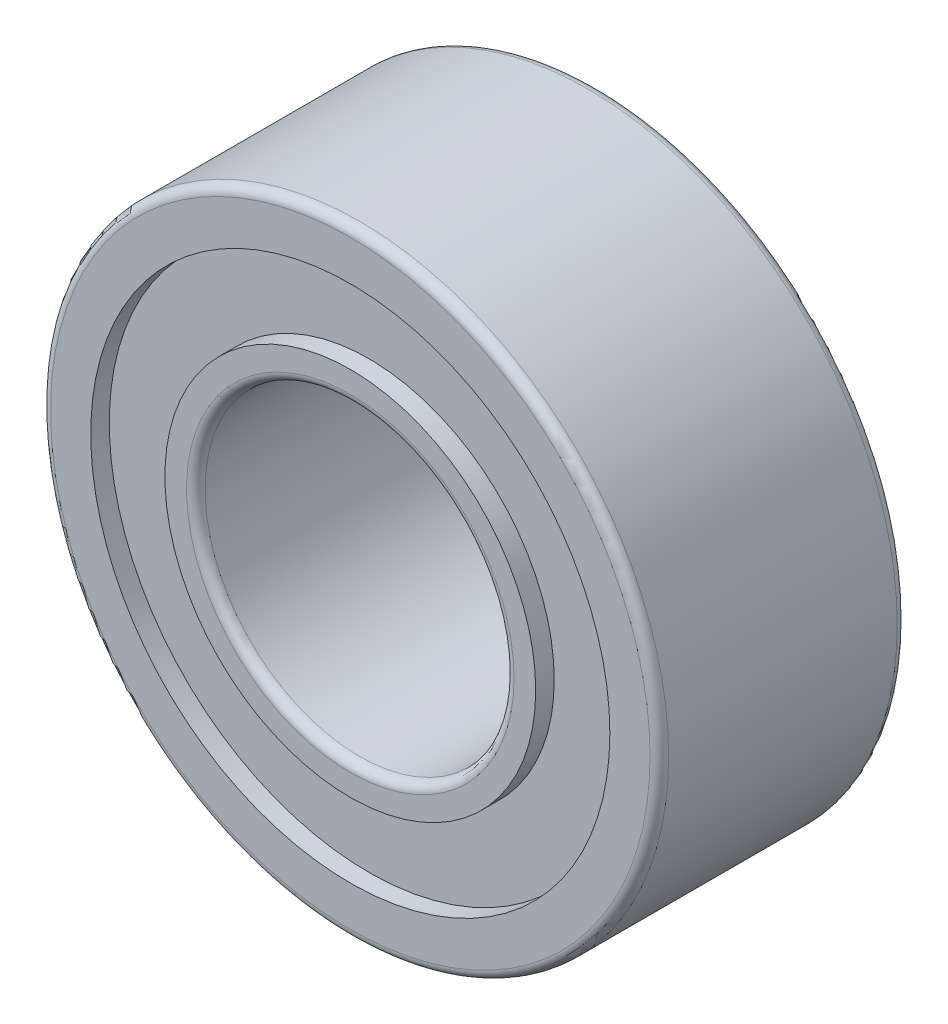
SolidWorks part; units mm, degrees
ref_plane "Front Plane" through (0, 0, 0) normal (0, 0, 1) x (1, 0, 0)
ref_plane "Top Plane" through (0, 0, 0) normal (0, 1, 0) x (1, 0, 0)
ref_plane "Right Plane" through (0, 0, 0) normal (1, 0, 0) x (0, 0, -1)
sketch "Sketch1" plane through (0, 0, 0) normal (0, 0, 1) x (1, 0, 0)
  circle A0 centre (0, 0) radius 2.5
  circle A1 centre (0, 0) radius 5
  dimension "D1" = 5
  dimension "D2" = 10
extrude "Boss-Extrude1" add sketch "Sketch1" along normal blind 4
sketch "Sketch2" plane through (0, 0, 4) normal (0, 0, 1) x (1, 0, 0)
  circle A3 centre (0, 0) radius 4.2
  circle A6 centre (0, 0) radius 3
  dimension "D1" = 6
  dimension "D2" = 8.4
extrude "Cut-Extrude1" cut sketch "Sketch2" against normal blind 0.3
extrude "Cut-Extrude2" cut sketch "Sketch2<2>" along normal blind 0.5 from surface starting at face at (5, 0, 0)
sketch "Sketch2<2>" plane through (0, 0, 4) normal (0, 0, 1) x (1, 0, 0) same geometry as "Sketch2"
fillet "Fillet1" radius 0.15 4 edges at (2.5, 0, 4) (5, 0, 4) (2.5, 0, 0) (5, 0, 0)
